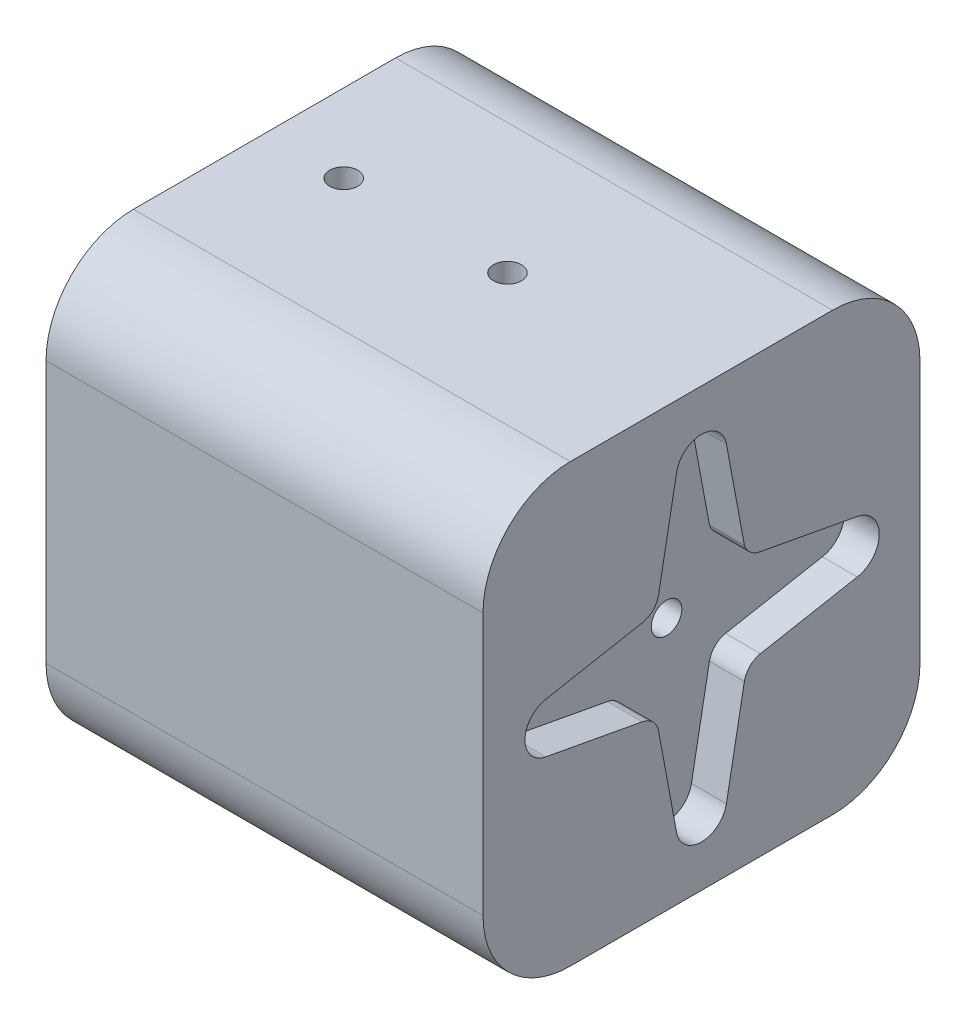
SolidWorks part; units mm, degrees
ref_plane "Plan de face" through (0, 0, 0) normal (0, 0, 1) x (1, 0, 0)
ref_plane "Plan de dessus" through (0, 0, 0) normal (0, 1, 0) x (1, 0, 0)
ref_plane "Plan de droite" through (0, 0, 0) normal (1, 0, 0) x (0, 0, -1)
sketch "Esquisse1" plane through (0, 0, 0) normal (0, 0, 1) x (1, 0, 0)
  line L1 (0, 0) -> (50, 0)
  line L2 (0, 0) -> (0, 50)
  line L3 (0, 50) -> (50, 50)
  line L4 (50, 0) -> (50, 50)
  dimension "D1" = 50
  dimension "D2" = 50
extrude "Boss.-Extru.1" add sketch "Esquisse1" along normal blind 50
sketch "Esquisse2" plane through (0, 0, 0) normal (-1, 0, 0) x (0, 0, 1)
  circle A0 centre (24.9769, 24.8563) radius 6
  dimension "D1" = 12
extrude "Enlèv. mat.-Extru.1" cut sketch "Esquisse2" against normal blind 40
fillet "Congé1" radius 10 4 edges at (25, 0, 50) (25, 50, 0) (25, 50, 50) (25, 0, 0)
sketch "Esquisse3" plane through (0, 50, 0) normal (0, 1, 0) x (1, 0, 0)
  circle A0 centre (8.9582, -24.8946) radius 1.6
  circle A1 centre (27.6954, -24.8946) radius 1.6
  dimension "D1" = 3.2
  dimension "D2" = 3.2
extrude "Enlèv. mat.-Extru.2" cut sketch "Esquisse3" against normal blind 21
sketch "Esquisse4" plane through (50, 0, 0) normal (1, 0, 0) x (0, 0, -1)
  line L0 (-14.6472, 30.3429) -> (-14.6472, 73.4856) construction
  line L1 (-7.1447, 28.1358) -> (-18.2242, 30.1928)
  line L2 (-20.0917, 31.7498) -> (-22.1487, 42.8294)
  line L3 (-27.8512, 42.8294) -> (-29.9083, 31.7498)
  line L4 (-31.7498, 29.9083) -> (-42.8293, 27.8513)
  line L5 (-42.8293, 22.1488) -> (-31.7498, 20.0917)
  line L6 (-29.9083, 18.2502) -> (-27.8512, 7.1707)
  line L7 (-22.1487, 7.1707) -> (-20.0917, 18.2502)
  line L8 (-18.2502, 20.0917) -> (-7.1706, 22.1488)
  line L12 (0, 10) -> (0, 40) construction
  line L14 (-40, 50) -> (-10, 50) construction
  arc A0 (-7.1706, 22.1488) -> (-7.1447, 28.1358) centre (-7.7, 25.1446) ccw
  arc A1 (-20.0917, 31.7498) -> (-18.2242, 30.1928) centre (-17.9076, 32.471) ccw
  arc A2 (-22.1487, 42.8294) -> (-27.8512, 42.8294) centre (-25, 42.3) ccw
  arc A3 (-31.7498, 29.9083) -> (-29.9083, 31.7498) centre (-32.1696, 32.1697) ccw
  arc A4 (-42.8293, 27.8513) -> (-42.8293, 22.1488) centre (-42.2999, 25) ccw
  arc A5 (-29.9083, 18.2502) -> (-31.7498, 20.0917) centre (-32.1696, 17.8304) ccw
  arc A6 (-27.8512, 7.1707) -> (-22.1487, 7.1707) centre (-25, 7.7001) ccw
  arc A7 (-18.2502, 20.0917) -> (-20.0917, 18.2502) centre (-17.8303, 17.8304) ccw
  dimension "D2" = 7.7
  dimension "D1" = 7.7
extrude "Enlèv. mat.-Extru.3" cut sketch "Esquisse4" against normal blind 4
sketch "Esquisse5" plane through (46, 0, 0) normal (1, 0, 0) x (0, 0, -1)
  line L0 (-30.5433, 30.5434) -> (-19.4566, 19.4567) construction
  line L1 (-30.5433, 19.4567) -> (-19.3805, 30.7044) construction
  circle A0 centre (-25, 25) radius 1.75
  arc A1 (-31.7498, 29.9083) -> (-29.9083, 31.7498) centre (-32.1696, 32.1697) ccw construction
  arc A2 (-18.2502, 20.0917) -> (-20.0917, 18.2502) centre (-17.8303, 17.8304) ccw construction
  arc A3 (-29.9083, 18.2502) -> (-31.7498, 20.0917) centre (-32.1696, 17.8304) ccw construction
  arc A4 (-20.0917, 31.7498) -> (-18.2242, 30.1928) centre (-17.9076, 32.471) ccw construction
  dimension "D1" = 3.5
extrude "Enlèv. mat.-Extru.4" cut sketch "Esquisse5" against normal blind 90
sketch "Esquisse6" plane through (0, 0, 0) normal (0, 0, -1) x (-1, 0, 0)
  line L1 (-50, 10) -> (0, 10) construction
  circle A0 centre (-20.4207, 25) radius 1.6
  dimension "D1" = 3.2
  dimension "D2" = 15
extrude "Enlèv. mat.-Extru.5" cut sketch "Esquisse6" against normal blind 20
